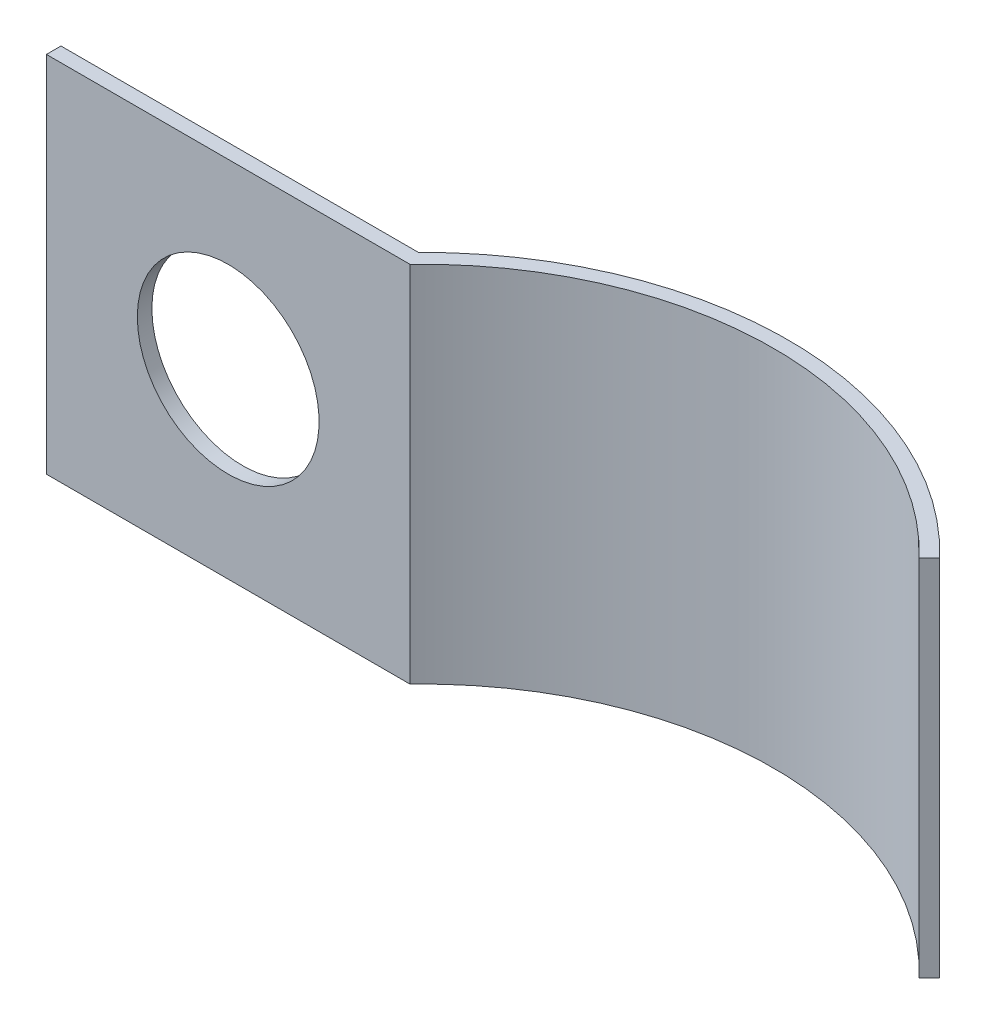
SolidWorks part; units mm, degrees
ref_plane "前视基准面" through (0, 0, 0) normal (0, 0, 1) x (1, 0, 0)
ref_plane "上视基准面" through (0, 0, 0) normal (0, 1, 0) x (1, 0, 0)
ref_plane "右视基准面" through (0, 0, 0) normal (1, 0, 0) x (0, 0, -1)
other "Configuration Table"
sketch "草图1" plane through (0, 0, 0) normal (0, 1, 0) x (1, 0, 0)
  line L0 (0, 0) -> (5, 0)
  line L6 (-991, 1.5) -> (49009, 1.5) construction
  line L7 (0, 0.2) -> (4.9153, 0.2)
  line L9 (0, 0) -> (0, 0.2)
  line L11 (12, 0) -> (13.0579, -1.0085) construction
  line L12 (12.1415, 0.1415) -> (13.1959, -0.8638) construction
  line L13 (12.1415, 0.1415) -> (12, 0)
  line L14 (-995, 0) -> (49005, 0) construction
  arc A0 (5, 0) -> (12, 0) centre (8.5, -3.3333) cw
  arc A1 (4.9153, 0.2) -> (12.1415, 0.1415) centre (8.5, -3.3333) cw
  point P10 (8.5, 1.5)
  dimension "D4" = 1.5
  dimension "D1" = 7
  dimension "D2" = 5
  dimension "D3" = 45
  dimension "D5" = 0.2
extrude "凸台-拉伸1" add sketch "草图1" along normal blind 5
sketch "草图2" plane through (0, 0, -0.2) normal (0, 0, -1) x (-1, 0, 0)
  line L0 (-1000, 2.5) -> (49000, 2.5) construction
  line L1 (0, 5) -> (0, 0) construction
  circle A0 centre (-2.5, 2.5) radius 1.25
  point P7 (0, 2.5)
  dimension "D1" = 2.5
  dimension "D2" = 2.5
extrude "切除-拉伸1" cut sketch "草图2" against normal blind 5
